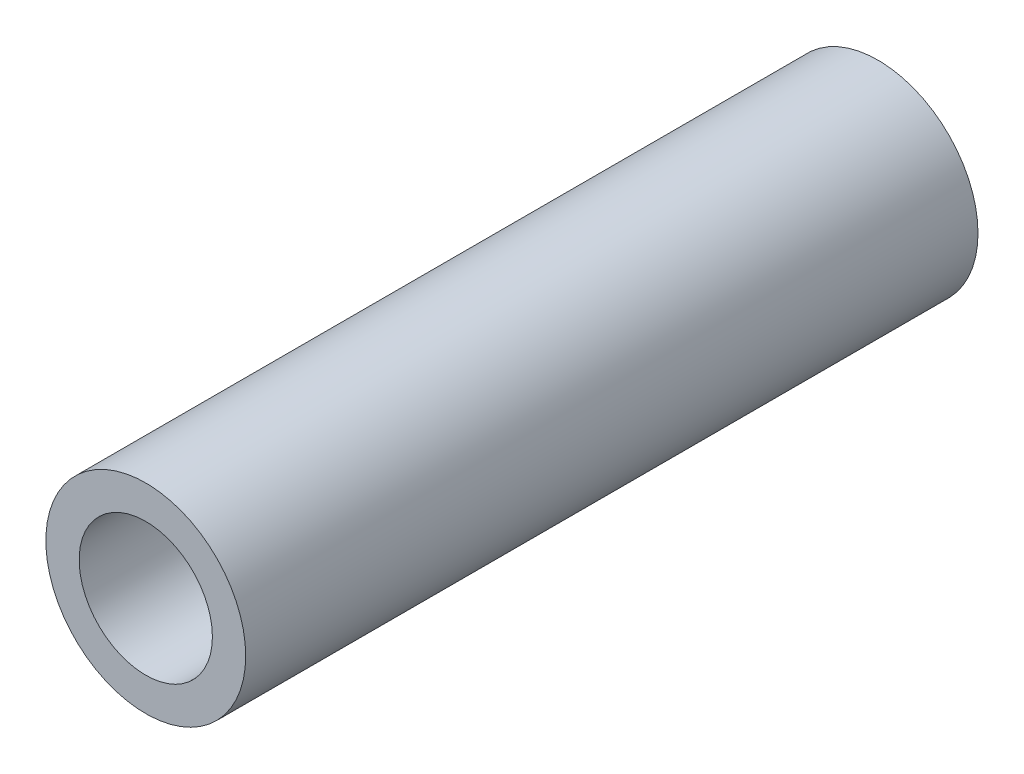
SolidWorks part; units mm, degrees
material "6061 Alloy"
ref_plane "Front Plane" through (0, 0, 0) normal (0, 0, 1) x (1, 0, 0)
ref_plane "Top Plane" through (0, 0, 0) normal (0, 1, 0) x (1, 0, 0)
ref_plane "Right Plane" through (0, 0, 0) normal (1, 0, 0) x (0, 0, -1)
sketch "Sketch1" plane through (0, 0, 0) normal (0, 0, 1) x (1, 0, 0)
  circle A0 centre (0, 0) radius 2.3813 construction
  dimension "Diameter" = 4.7625
sketch "Sketch2" plane through (0, 0, 0) normal (1, 0, 0) x (0, 0, -1)
  line L0 (-65.3546, 0) -> (65.3546, 0) construction
  line L1 (-65.3546, 2.3813) -> (65.3546, 2.3813) construction
  line L2 (-65.3546, 0.7971) -> (-65.3546, -43.7047) construction
  line L3 (0, 2.3813) -> (0, -2.3813) construction
  point P0 (-39.9546, 0)
  point P3 (0, 0)
  point P4 (39.9546, 0)
  point P6 (76.2, 2.3813)
  point P9 (0, 2.3813)
  point P12 (18.492, 2.3813)
  point P14 (0.9293, 2.3813)
  point P15 (-8.2046, 2.3813)
  point P16 (0, 0)
  point P17 (-11.3796, 2.3813)
  point P20 (0, 0)
  point P21 (0, 0)
  dimension "D1" = 25.4
  dimension "Length" = 130.7092
  dimension "D2" = 25.4
sketch "Sketch3" plane through (0, 0, 0) normal (0, 0, 1) x (1, 0, 0)
  circle A0 centre (0, 0) radius 2.3813 construction
  circle A1 centre (0, 0) radius 2.3813
extrude "Boss-Extrude1" add sketch "Sketch3" against normal up to vertex (65.3546 mm away) from vertex up to point (0, 0, -65.3546) starting at point (0, 0, 65.3546)
ref_plane "Plane1" through (0, 0, 44.7296) normal (0, 0, 1) x (1, 0, 0)
sketch "Sketch4" plane through (0, 0, -65.3546) normal (0, 0, -1) x (-1, 0, 0)
  circle A0 centre (0, 0) radius 2.3813 construction
  circle A1 centre (0, 0) radius 2.3813
extrude "Cut-Extrude1" cut sketch "Sketch4" against normal up to surface (110.0842 mm away) up to plane "Plane1"
ref_plane "Plane2" through (0, 0, 62.1796) normal (0, 0, 1) x (1, 0, 0)
sketch "Sketch5" plane through (0, 0, 62.1796) normal (0, 0, 1) x (1, 0, 0)
  circle A0 centre (0, 0) radius 2.3813 construction
  circle A1 centre (0, 0) radius 2.3813
extrude "Cut-Extrude2" cut sketch "Sketch5" along normal through all
hole_wizard "1/8 (0.125) Diameter Hole1" positions "Sketch6" profile "Sketch7" hole size "1/8" standard "ANSI Inch" end condition up to next
sketch "Sketch6" plane through (0, 0, 62.1796) normal (0, 0, 1) x (1, 0, 0)
  point P0 (0, 0)
sketch "Sketch7" plane through (0, 0, 62.1796) normal (1, 0, 0) x (0, -1, 0)
  line L0 (0, 0) -> (0, 17.45)
  line L1 (0, 17.45) -> (1.5875, 17.45)
  line L2 (1.5875, 17.45) -> (1.5875, 0)
  line L5 (1.5875, 0) -> (0, 0)
  line L11 (0, -6.35) -> (0, 107.95) construction
  dimension "Thru Hole Dia." = 3.175
  dimension "Thru Hole Depth" = 17.45
